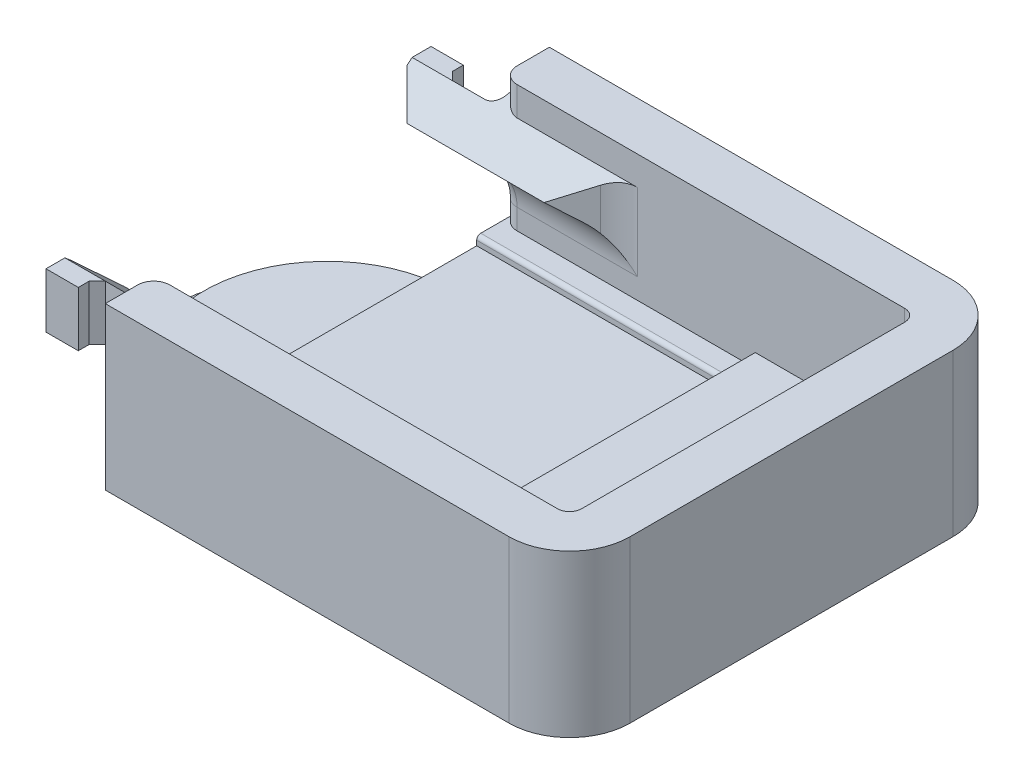
SolidWorks part; units mm, degrees
ref_plane "Alzado" through (0, 0, 0) normal (0, 0, 1) x (1, 0, 0)
ref_plane "Planta" through (0, 0, 0) normal (0, 1, 0) x (1, 0, 0)
ref_plane "Vista lateral" through (0, 0, 0) normal (1, 0, 0) x (0, 0, -1)
sketch "Croquis1" plane through (0, 0, 0) normal (0, 1, 0) x (1, 0, 0)
  line L0 (28.75, 0) -> (-28.75, 0) construction
  line L1 (25, 13.75) -> (-25, 13.75)
  line L2 (25, -13.75) -> (-25, -13.75)
  line L3 (-28.75, 10) -> (-28.75, -10)
  line L4 (28.75, 10) -> (28.75, -10)
  line L5 (0, -13.75) -> (0, 13.75) construction
  arc A0 (28.75, -10) -> (25, -13.75) centre (25, -10) cw
  arc A1 (-25, -13.75) -> (-28.75, -10) centre (-25, -10) cw
  arc A2 (28.75, 10) -> (25, 13.75) centre (25, 10) ccw
  arc A3 (-25, 13.75) -> (-28.75, 10) centre (-25, 10) ccw
  point P3 (0, 0)
  point P18 (0, 0)
  dimension "D1" = 3.75
  dimension "D2" = 57.5
  dimension "D3" = 27.5
  dimension "D4" = 10
extrude "Saliente-Extruir1" add sketch "Croquis1" along normal blind 3
sketch "Croquis2" plane through (0, 0, 0) normal (0, -1, 0) x (1, 0, 0)
  line L0 (25, -13.75) -> (-25, -13.75) construction
  circle A1 centre (0, 0) radius 7.63
  point P3 (0, -13.75)
  dimension "D1" = 15.26
extrude "Saliente-Extruir2" add sketch "Croquis2" along normal blind 3
sketch "Croquis3" plane through (0, 0, 0) normal (0, 0, 1) x (1, 0, 0)
  line L0 (7.63, -1.0671) -> (7.63, -3)
  line L1 (7.73, -1) -> (7.73, -3) construction
  line L2 (7.63, -1.0671) -> (9.73, -1.9262)
  line L3 (7.73, -1) -> (9.93, -1.9) construction
  line L4 (0, -3) -> (7.73, -3) construction
  line L5 (9.93, -1.9) -> (9.93, -3) construction
  line L6 (9.93, -3) -> (7.73, -3) construction
  line L7 (9.73, -3) -> (9.73, -1.9262) construction
  line L8 (7.73, -1.108) -> (9.73, -1.9262) construction
  line L9 (9.73, -1.9262) -> (9.73, -3)
  line L11 (7.73, -1.108) -> (7.73, -3) construction
  line L12 (-7.63, -3) -> (7.63, -3) construction
  line L13 (0, -3) -> (0, 0) construction
  line L14 (7.63, -3) -> (7.63, 0) construction
  line L15 (7.63, -3) -> (9.73, -3)
  dimension "D1" = 2.2
  dimension "D2" = 1.1
  dimension "D3" = 0.2
  dimension "D4" = 0.1
  dimension "D5" = 7.73
  dimension "D6" = 112.249
revolve "Revolución1" add sketch "Croquis3" angle 45 about L13 other way angle 15
sketch "Croquis5" plane through (0, 0, 0) normal (0, 0, 1) x (1, 0, 0)
  line L1 (-7.63, -3) -> (7.37, -3) construction
  line L3 (7.63, -1.0671) -> (7.63, -3) construction
  line L11 (7.73, -1) -> (7.73, -3) construction
  line L12 (-9.73, -1.9262) -> (-9.73, -3)
  line L13 (7.63, -1.0671) -> (9.73, -1.9262) construction
  line L18 (-7.63, -3) -> (-9.73, -3)
  line L19 (7.73, -1) -> (9.93, -1.9) construction
  line L20 (0, -3) -> (7.73, -3) construction
  line L25 (9.93, -1.9) -> (9.93, -3) construction
  line L26 (9.93, -3) -> (7.73, -3) construction
  line L27 (9.73, -3) -> (9.73, -1.9262) construction
  line L28 (7.73, -1.108) -> (9.73, -1.9262) construction
  line L29 (9.73, -1.9262) -> (9.73, -3) construction
  line L30 (7.73, -1.108) -> (7.73, -3) construction
  line L31 (0, -3) -> (0, 0) construction
  line L32 (7.63, -3) -> (9.73, -3) construction
  line L33 (-7.63, -1.0671) -> (-7.63, -3)
  line L34 (-7.63, -1.0671) -> (-9.73, -1.9262)
  dimension "D1" = 2.2
  dimension "D2" = 1.1
  dimension "D3" = 0.2
  dimension "D4" = 112.249
  dimension "D5" = 7.73
  dimension "D6" = 0.1
  dimension "D7" = 1.9329
revolve "Revolución2" add sketch "Croquis5" angle 45 about L31 other way angle 15
sketch "Croquis6" plane through (0, -3, 0) normal (0, -1, 0) x (1, 0, 0)
  line L0 (0, 0) -> (9.5627, -2.5623) construction
  line L1 (0, 0) -> (-9.5627, 2.5623) construction
  circle A2 centre (-9.5627, 2.5623) radius 1
  circle A3 centre (9.5627, -2.5623) radius 1
  dimension "D1" = 2
  dimension "D2" = 15
  dimension "D3" = 9.9
extrude "Cortar-Extruir1" cut sketch "Croquis6" against normal up to next
fillet "Redondeo4" radius 1 14 edges at (9.3985, -2.4631, 2.5183) (9.0986, -2.4631, -3.4481) (9.6036, -2.4631, -1.5631) (6.8801, -2.4631, -6.8801) (5.3952, -2.0336, -5.3952) (7.37, -2.0336, 1.9748) (-7.37, -2.0336, -1.9748) (-9.3985, -2.4631, -2.5183) (-9.6036, -2.4631, 1.5631) (-9.0986, -2.4631, 3.4481) (-5.3952, -2.0336, 5.3952) (-6.8801, -2.4631, 6.8801) (-7.37, -1.0671, 1.9748) (7.37, -1.0671, -1.9748)
sketch "Croquis8" plane through (0, 3, 0) normal (0, 1, 0) x (1, 0, 0)
  line L0 (25, 10.75) -> (-25, 10.75)
  line L1 (-25.75, 10) -> (-25.75, -10)
  line L2 (-25, -10.75) -> (25, -10.75)
  line L3 (25.75, -10) -> (25.75, 10)
  line L4 (28.75, -10) -> (28.75, 10)
  line L5 (25, 13.75) -> (-25, 13.75)
  line L6 (-28.75, 10) -> (-28.75, -10)
  line L7 (-25, -13.75) -> (25, -13.75)
  line L8 (28.75, -10) -> (28.75, 10)
  line L9 (25, 13.75) -> (-25, 13.75)
  line L10 (-28.75, 10) -> (-28.75, -10)
  line L11 (-25, -13.75) -> (25, -13.75)
  arc A0 (-25, 10.75) -> (-25.75, 10) centre (-25, 10) ccw
  arc A1 (-25.75, -10) -> (-25, -10.75) centre (-25, -10) ccw
  arc A2 (25, -10.75) -> (25.75, -10) centre (25, -10) ccw
  arc A3 (25.75, 10) -> (25, 10.75) centre (25, 10) ccw
  arc A4 (25, -13.75) -> (28.75, -10) centre (25, -10) ccw
  arc A5 (28.75, 10) -> (25, 13.75) centre (25, 10) ccw
  arc A6 (-25, 13.75) -> (-28.75, 10) centre (-25, 10) ccw
  arc A7 (-28.75, -10) -> (-25, -13.75) centre (-25, -10) ccw
  arc A8 (25, -13.75) -> (28.75, -10) centre (25, -10) ccw
  arc A9 (28.75, 10) -> (25, 13.75) centre (25, 10) ccw
  arc A10 (-25, 13.75) -> (-28.75, 10) centre (-25, 10) ccw
  arc A11 (-28.75, -10) -> (-25, -13.75) centre (-25, -10) ccw
  dimension "D1" = 0
  dimension "D2" = 3
extrude "Saliente-Extruir3" add sketch "Croquis8" along normal blind 7
sketch "Croquis9" plane through (0, 0, 0) normal (0, 0, 1) x (1, 0, 0)
  line L0 (0, 10) -> (0, 3)
  line L1 (0, 3) -> (15.75, 3)
  line L2 (15.75, 3) -> (15.75, 1.6)
  line L3 (15.75, 1.6) -> (0, 1.6)
  line L4 (0, 1.6) -> (0, 0)
  line L5 (0, 0) -> (-9.73, 0)
  line L6 (-9.73, 0) -> (-9.73, -3) construction
  line L7 (-9.73, -3) -> (28.75, -3) construction
  line L8 (0, 10) -> (28.75, 10) construction
  line L9 (28.75, 10) -> (28.75, -3) construction
  line L10 (28.75, 10) -> (25, 10) construction
  line L11 (28.75, 10) -> (28.75, 0) construction
  line L12 (0, 10) -> (-28.75, 10)
  line L13 (-28.75, 10) -> (-28.75, 0)
  line L14 (-28.75, 0) -> (-9.73, 0)
  dimension "D1" = 1.4
  dimension "D2" = 28.75
  dimension "D3" = 7
  dimension "D4" = 13
  dimension "D5" = 15.75
  dimension "D6" = 38.48
  dimension "D7" = 3
  dimension "D8" = 9.73
extrude "Cortar-Extruir2" cut sketch "Croquis9" against normal through all both and the other way through all
ref_plane "Plano1" through (25, 0, 0) normal (1, 0, 0) x (0, 0, -1)
sketch "Croquis13" plane through (25, 0, 0) normal (1, 0, 0) x (0, 0, -1)
  line L0 (-13.75, 3) -> (-10.75, 3)
  line L1 (-13.75, 3) -> (-13.75, 1.6)
  line L2 (-13.75, 1.6) -> (-9.25, 1.6)
  line L3 (-10.75, 3) -> (-10.75, 2.15)
  line L4 (-10.75, 2.15) -> (-9.25, 2.15)
  line L5 (-9.25, 2.15) -> (-9.25, 1.6)
  line L6 (0, 0) -> (0, 10) construction
  line L7 (-10, 10) -> (10, 10) construction
  line L8 (13.75, 3) -> (13.75, 1.6)
  line L9 (13.75, 1.6) -> (9.25, 1.6)
  line L10 (9.25, 2.15) -> (9.25, 1.6)
  line L11 (10.75, 2.15) -> (9.25, 2.15)
  line L12 (10.75, 3) -> (10.75, 2.15)
  line L13 (13.75, 3) -> (10.75, 3)
  dimension "D1" = 0.85
  dimension "D2" = 1.5
  dimension "D3" = 4.5
extrude "Saliente-Extruir4" add sketch "Croquis13" against normal up to surface and the other way up to surface up to face at (0, 6.5, -12.25) other way up to face at (25.75, 6.5, 0)
sketch "Croquis15" plane through (0, 0, 0) normal (0, 1, 0) x (1, 0, 0)
  line L2 (25, -13.75) -> (25.75, -13.75)
  line L3 (25.75, -13.75) -> (25.75, -13.6742)
  line L4 (25, -13.75) -> (25.75, -13.75)
  line L5 (25.75, -13.75) -> (25.75, -13.6742)
  line L6 (25.75, 13.6742) -> (25.75, 13.75)
  line L7 (25.75, 13.75) -> (25, 13.75)
  line L8 (25.75, 13.6742) -> (25.75, 13.75)
  line L9 (25.75, 13.75) -> (25, 13.75)
  arc A1 (25, -13.75) -> (25.75, -13.6742) centre (25, -10) ccw
  arc A2 (25, -13.75) -> (25.75, -13.6742) centre (25, -10) ccw
  arc A3 (25.75, 13.6742) -> (25, 13.75) centre (25, 10) ccw
  arc A4 (25.75, 13.6742) -> (25, 13.75) centre (25, 10) ccw
  dimension "D1" = 0
  dimension "D2" = 0
extrude "Cortar-Extruir3" cut sketch "Croquis15" along normal through all both and the other way through all
fillet "Redondeo12" radius 0.25 2 edges at (7.875, 2.15, -9.25) (7.875, 2.15, 9.25)
sketch "Croquis17" plane through (0, 0, 0) normal (0, 0, 1) x (1, 0, 0)
  line L0 (25.75, 6.505) -> (23.75, 6.505) construction
  line L1 (25.75, 10) -> (25.75, 3) construction
  line L2 (23.75, 6.505) -> (25.75, 7.005)
  line L3 (25.75, 7.005) -> (25.75, 6.005)
  line L4 (25.75, 6.005) -> (23.75, 6.505)
  line L5 (28.75, 10) -> (25, 10) construction
  dimension "D1" = 2
  dimension "D2" = 1
  dimension "D3" = 3.495
extrude "Saliente-Extruir6" add sketch "Croquis17" along normal blind 5 and the other way blind 5
fillet "Redondeo14" radius 1 4 edges at (25.75, 6.505, -5) (25.75, 6.505, 5) (25.75, 6.005, 0) (25.75, 7.005, 0)
ref_plane "Plano2" through (0, 6.505, 0) normal (0, 1, 0) x (0, 0, 1)
sketch "Croquis21" plane through (0, 6.505, 0) normal (0, 1, 0) x (0, 0, 1)
  line L0 (10.75, 7.5) -> (10.75, -3)
  line L1 (-10.75, 0) -> (-10.75, 15.75) construction
  line L2 (10.75, -3) -> (11.25, -3.5)
  line L3 (11.25, -3.5) -> (13.75, -3.5) construction
  line L4 (-13.75, 0) -> (-10.75, 0) construction
  line L5 (11.25, -3.5) -> (11.9216, -3.5)
  line L6 (13.75, -3.5) -> (14.25, -2.5) construction
  line L8 (10.75, 7.5) -> (8.75, 4.6716)
  line L9 (8.75, 4.6716) -> (8.75, -3.8284)
  line L10 (8.75, -3.8284) -> (10.4216, -5.5)
  line L11 (10.4216, -5.5) -> (14.25, -5.5) construction
  line L12 (14.25, -5.5) -> (14.25, -3.5) construction
  line L13 (14.25, -3.5) -> (14.25, -2.5) construction
  line L14 (0, 13.75) -> (0, -13.75) construction
  line L15 (5, -13.75) -> (-5, -13.75) construction
  line L16 (11.9216, -3.5) -> (11.9216, -5.5)
  line L17 (-14.25, -5.5) -> (-14.25, -3.5) construction
  line L18 (-10.4216, -5.5) -> (-14.25, -5.5) construction
  line L19 (-8.75, -3.8284) -> (-10.4216, -5.5)
  line L20 (-8.75, 4.6716) -> (-8.75, -3.8284)
  line L21 (-10.75, 7.5) -> (-8.75, 4.6716)
  line L22 (-14.25, -2.5) -> (-14.25, -3.5) construction
  line L23 (-13.75, -3.5) -> (-14.25, -2.5) construction
  line L24 (-11.25, -3.5) -> (-13.75, -3.5) construction
  line L25 (-10.75, -3) -> (-11.25, -3.5)
  line L26 (-10.75, 7.5) -> (-10.75, -3)
  line L27 (11.9216, -5.5) -> (10.4216, -5.5)
  line L28 (-11.25, -3.5) -> (-11.9216, -3.5)
  line L29 (-11.9216, -3.5) -> (-11.9216, -5.5)
  line L30 (-11.9216, -5.5) -> (-10.4216, -5.5)
  dimension "D1" = 2
  dimension "D2" = 3.4641
  dimension "D3" = 8.5
  dimension "D4" = 2.364
  dimension "D5" = 3.8284
  dimension "D6" = 2
  dimension "D7" = 45
  dimension "D8" = 0.7071
  dimension "D9" = 63.435
  dimension "D10" = 1.118
  dimension "D11" = 7.5
  dimension "D12" = 1.5
  dimension "D13" = 1.5
extrude "Saliente-Extruir7" add sketch "Croquis21" along normal blind 1.7 and the other way blind 1.7
sketch "Croquis23" plane through (-5.5, 0, 0) normal (-1, 0, 0) x (0, 0, 1)
  line L0 (-10.75, 8.205) -> (-8.75, 6.505)
  line L1 (-8.75, 4.805) -> (-8.75, 8.205) construction
  line L2 (-8.75, 6.505) -> (-10.75, 4.805)
  line L3 (-10.75, 4.805) -> (10.75, 4.805)
  line L4 (10.75, 4.805) -> (8.75, 6.505)
  line L5 (8.75, 4.805) -> (8.75, 8.205) construction
  line L6 (8.75, 6.505) -> (10.75, 8.205)
  line L7 (10.75, 8.205) -> (10.75, 10)
  line L8 (10.75, 10) -> (-10.75, 10)
  line L9 (-10.75, 10) -> (-10.75, 8.205)
extrude "Cortar-Extruir4" cut sketch "Croquis23" against normal blind 15 and the other way through all
fillet "Redondeo19" radius 3 4 edges at (3.75, 4.805, 10.75) (3.75, 4.805, -10.75) (7.5, 6.505, 10.75) (7.5, 6.505, -10.75)
fillet "Redondeo16" radius 1 2 edges at (0, 6.505, 10.75) (0, 6.505, -10.75)
fillet "Redondeo20" radius 1 6 edges at (0, 2.7838, 10.75) (0, 4.6769, -10.4729) (0, 4.6769, 10.4729) (0, 9.1025, 10.75) (0, 2.7838, -10.75) (0, 9.1025, -10.75)
ref_axis "Eje1" through (0, 10.65, 0) along (0, -1, 0)
